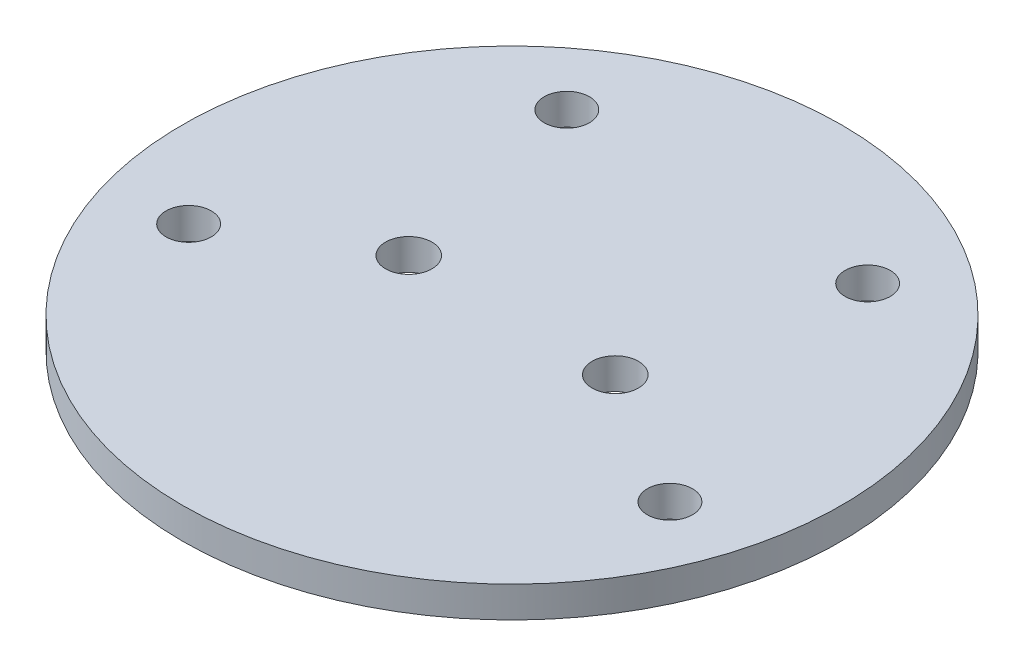
SolidWorks part; units mm, degrees
material "5052-H32"
ref_plane "Front Plane" through (0, 0, 0) normal (0, 0, 1) x (1, 0, 0)
ref_plane "Top Plane" through (0, 0, 0) normal (0, 1, 0) x (1, 0, 0)
ref_plane "Right Plane" through (0, 0, 0) normal (1, 0, 0) x (0, 0, -1)
sketch "Sketch1" plane through (0, 0, 0) normal (0, 1, 0) x (1, 0, 0)
  line L0 (0, 0) -> (-23.1297, 31.5565) construction
  line L1 (0, 0) -> (-41.7254, 0) construction
  line L2 (-37.0005, -12.7186) -> (0, 0) construction
  line L3 (0, -31.6103) -> (0, 47.1695) construction
  circle A0 centre (0, 0) radius 50.673
  circle A3 centre (-15.875, 0) radius 3.5687
  circle A4 centre (15.875, 0) radius 3.5687
  circle A5 centre (-37.0005, -12.7186) radius 3.475
  circle A8 centre (-23.1297, 31.5565) radius 3.475
  circle A9 centre (23.1297, 31.5565) radius 3.475
  circle A10 centre (37.0005, -12.7186) radius 3.475
  point P18 (0, 0)
  dimension "D1" = 101.346
  dimension "D2" = 6.95
  dimension "D3" = 6.95
  dimension "D10" = 7.1374
  dimension "D5" = 15.875
  dimension "D6" = 15.875
  dimension "D4" = 39.1254
  dimension "D7" = 53.76
  dimension "D8" = 39.1254
  dimension "D9" = 18.97
extrude "Boss-Extrude1" add sketch "Sketch1" along normal blind 4.7752
equation "\"allrockets_tube_ID\"= 3.85in"
equation "\"allrockets_tube_OD\"= 4.024in"
equation "\"hole\"= 6.35mm"
equation "\"back_plate_width\"= 28mm"
equation "\"card_spacing\"= 20mm"
equation "\"card_number\"= 5"
equation "\"ToDi\"= 0.05mm"
equation "\"card_diameter\"= 85.86mm"
equation "\"overlap\"= 6.6mm"
equation "\"card_length\"= 68mm"
equation "\"rack_hole_tol\"= 0.60mm"
equation "\"rack_front_width\"= 11.63mm"
equation "\"hole_b_d\"= 39.12541885mm"
equation "\"hole_b_a\"= 18.9721389deg"
equation "\"hole_u_d\"= 39.12541885mm"
equation "\"hole_u_a\"= 53.76090642deg"
equation "\"card_h\"= 61.73mm"
equation "\"sphinx_av\"= 50.292mm"
equation "\"tb_spacing\"= 40mm"
equation "\"D2@Sketch1\"=\"hole\"+\"rack_hole_tol\""
equation "\"D4@Sketch1\"=\"hole_u_d\""
equation "\"D7@Sketch1\"=\"hole_u_a\""
equation "\"D8@Sketch1\"=\"hole_b_d\""
equation "\"D9@Sketch1\"=\"hole_b_a\""
equation "\"D3@Sketch1\"=\"hole\"+\"rack_hole_tol\""
